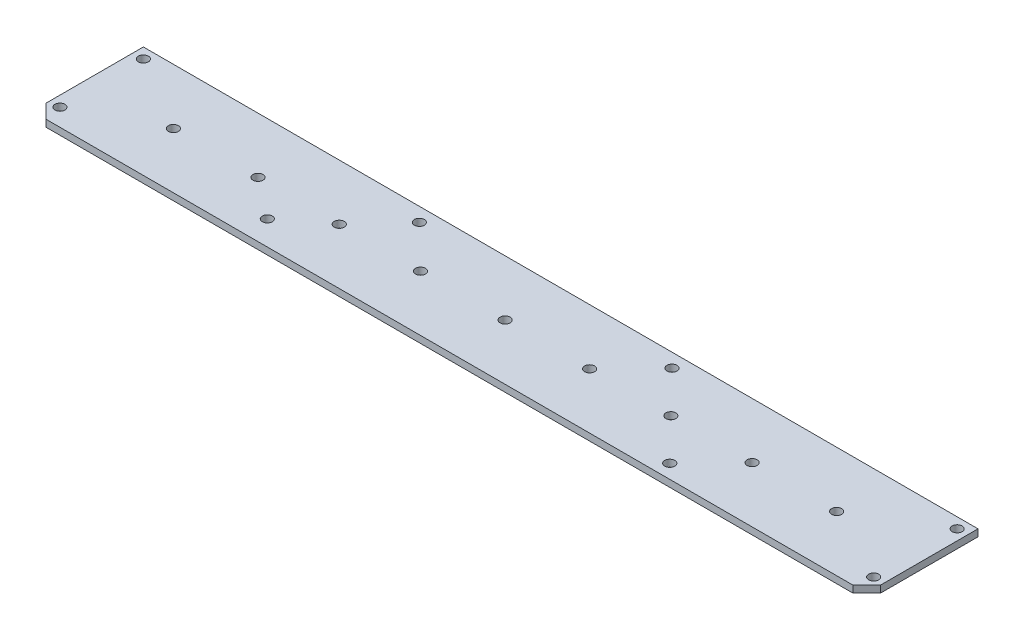
SolidWorks part; units mm, degrees
ref_plane "Front Plane" through (0, 0, 0) normal (0, 0, 1) x (1, 0, 0)
ref_plane "Top Plane" through (0, 0, 0) normal (0, 1, 0) x (1, 0, 0)
ref_plane "Right Plane" through (0, 0, 0) normal (1, 0, 0) x (0, 0, -1)
sketch "Sketch2" plane through (0, 0, 0) normal (0, 1, 0) x (1, 0, 0)
  line L0 (0, 0) -> (0, 50.8)
  line L1 (0, 50.8) -> (381, 50.8)
  line L2 (381, 50.8) -> (381, 0)
  line L3 (381, 0) -> (0, 0)
  dimension "D1" = 50.8
  dimension "D2" = 381
extrude "Boss-Extrude1" add sketch "Sketch2" along normal blind 3.175
sketch "Sketch3" plane through (0, 0, 0) normal (0, 1, 0) x (1, 0, 0)
  line L0 (0, 6.35) -> (6.35, 0) construction
  line L1 (374.65, 0) -> (381, 6.35) construction
  line L2 (0, 6.35) -> (6.35, 0)
  line L3 (374.65, 0) -> (381, 6.35)
  line L4 (0, 6.35) -> (0, 0)
  line L5 (0, 0) -> (6.35, 0)
  line L7 (381, 6.35) -> (381, 0)
  line L8 (381, 0) -> (374.65, 0)
  circle A19 centre (96.266, 11.1125) radius 2.286 construction
  circle A20 centre (284.734, 6.35) radius 2.286 construction
  circle A22 centre (132.334, 44.45) radius 2.286 construction
  circle A23 centre (247.65, 44.45) radius 2.286 construction
  circle A26 centre (4.7625, 7.9375) radius 2.286 construction
  circle A27 centre (4.7625, 46.0375) radius 2.286 construction
  circle A28 centre (39.116, 25.4) radius 2.286 construction
  circle A29 centre (77.724, 25.4) radius 2.286 construction
  circle A30 centre (114.808, 25.4) radius 2.286 construction
  circle A32 centre (190.5, 25.4) radius 2.286 construction
  circle A36 centre (341.884, 25.4) radius 2.286 construction
  circle A37 centre (376.2375, 7.9375) radius 2.286 construction
  circle A38 centre (376.2375, 46.0375) radius 2.286 construction
  circle A39 centre (96.266, 11.1125) radius 2.286
  circle A40 centre (284.734, 6.35) radius 2.286
  circle A42 centre (132.334, 44.45) radius 2.286
  circle A43 centre (247.65, 44.45) radius 2.286
  circle A46 centre (4.7625, 7.9375) radius 2.286
  circle A47 centre (4.7625, 46.0375) radius 2.286
  circle A48 centre (39.116, 25.4) radius 2.286
  circle A49 centre (77.724, 25.4) radius 2.286
  circle A50 centre (114.808, 25.4) radius 2.286
  circle A52 centre (190.5, 25.4) radius 2.286
  circle A56 centre (341.884, 25.4) radius 2.286
  circle A57 centre (376.2375, 7.9375) radius 2.286
  circle A58 centre (376.2375, 46.0375) radius 2.286
  circle A59 centre (303.276, 25.4) radius 2.286
  circle A60 centre (266.192, 25.4) radius 2.286
  circle A61 centre (229.108, 25.4) radius 2.286
  circle A62 centre (151.892, 25.4) radius 2.286
  dimension "D1" = 4.572
extrude "Cut-Extrude1" cut sketch "Sketch3" along normal through all
